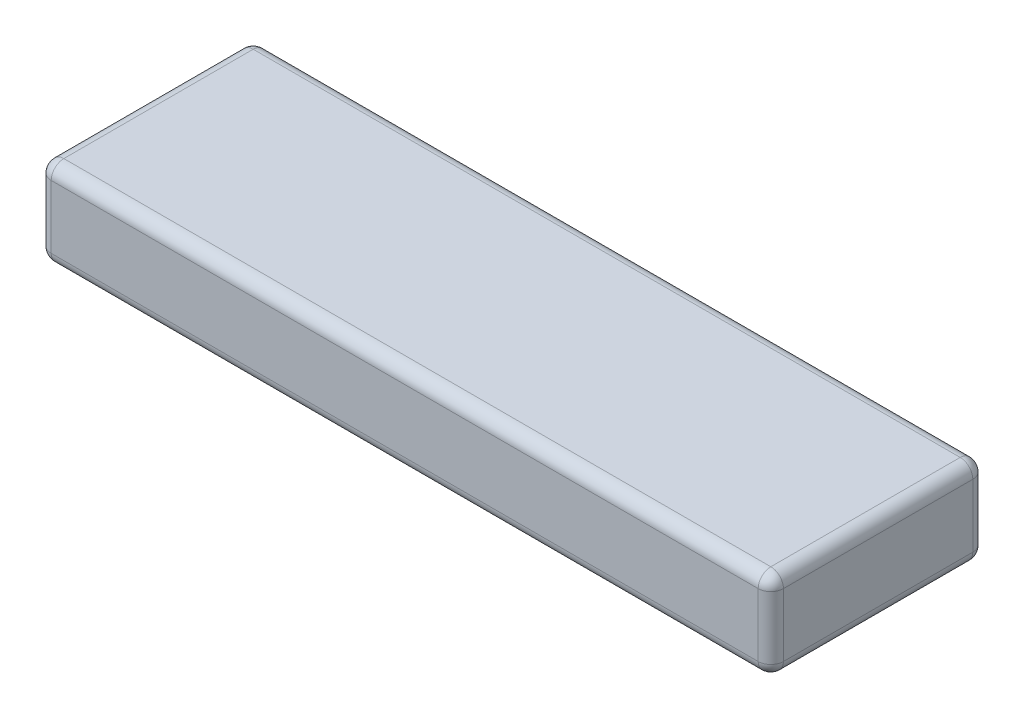
SolidWorks part; units mm, degrees
ref_plane "Plano frontal" through (0, 0, 0) normal (0, 0, 1) x (1, 0, 0)
ref_plane "Plano superior" through (0, 0, 0) normal (0, 1, 0) x (1, 0, 0)
ref_plane "Plano direito" through (0, 0, 0) normal (1, 0, 0) x (0, 0, -1)
sketch "Esboço1" plane through (0, 0, 0) normal (0, 1, 0) x (1, 0, 0)
  line L1 (0, 0) -> (116, 0)
  line L2 (0, 0) -> (0, 34)
  line L3 (0, 34) -> (116, 34)
  line L4 (116, 0) -> (116, 34)
  dimension "D1" = 116
  dimension "D2" = 34
extrude "Ressalto-extrusão1" add sketch "Esboço1" along normal blind 14
fillet "Filete1" radius 2 8 edges at (58, 0, 0) (116, 0, -17) (58, 0, -34) (0, 0, -17) (58, 14, -34) (116, 14, -17) (58, 14, 0) (0, 14, -17)
fillet "Filete2" radius 2 12 edges at (0.5858, 13.4142, -0.5858) (0.5858, 0.5858, -0.5858) (0.5858, 13.4142, -33.4142) (0.5858, 0.5858, -33.4142) (115.4142, 13.4142, -33.4142) (115.4142, 0.5858, -33.4142) (115.4142, 13.4142, -0.5858) (115.4142, 0.5858, -0.5858) (0, 7, 0) (0, 7, -34) (116, 7, -34) (116, 7, 0)
